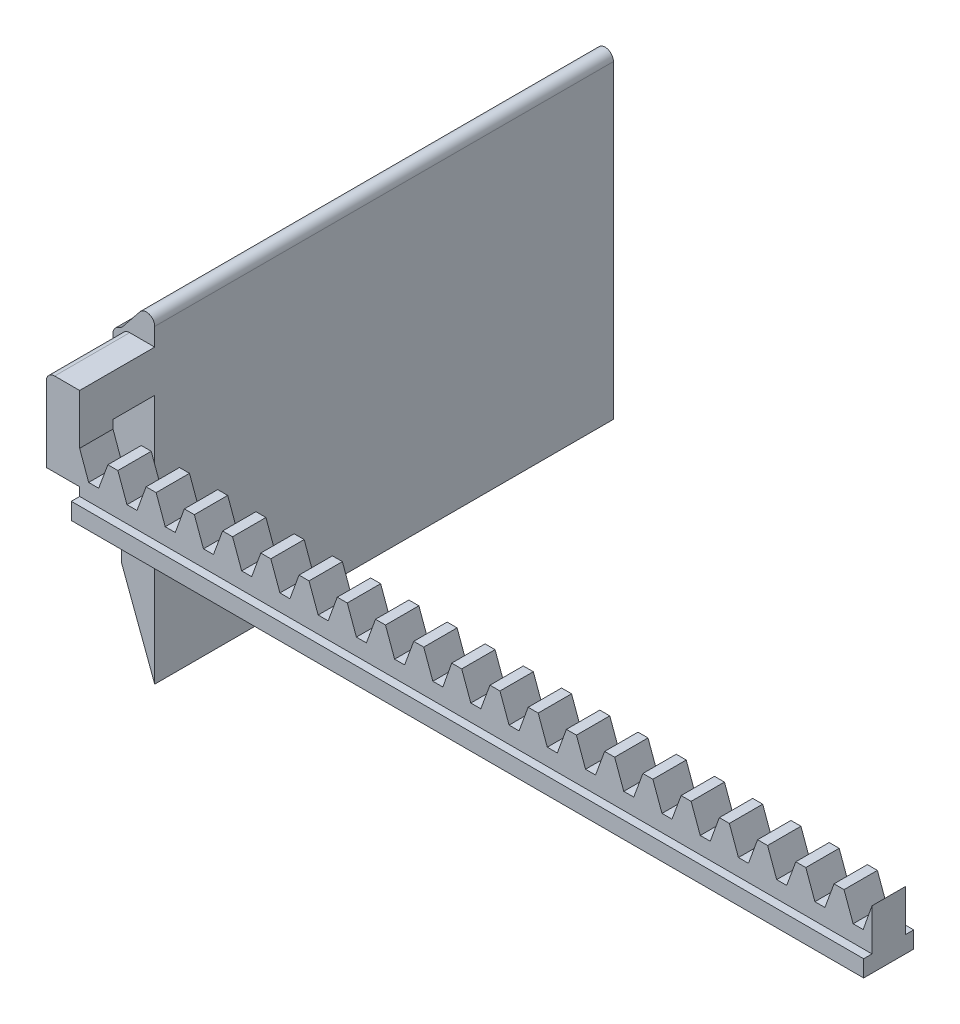
SolidWorks part; units mm, degrees
ref_plane "Plan de face" through (0, 0, 0) normal (0, 0, 1) x (1, 0, 0)
ref_plane "Plan de dessus" through (0, 0, 0) normal (0, 1, 0) x (1, 0, 0)
ref_plane "Plan de droite" through (0, 0, 0) normal (1, 0, 0) x (0, 0, -1)
sketch "Esquisse2" plane through (0, 0, 0) normal (0, 0, 1) x (1, 0, 0)
  line L0 (-0.6, 0) -> (0.6, 0)
  line L1 (-0.6, 0) -> (-1.6919, 3)
  line L2 (0.6, 0) -> (1.6919, 3)
  line L3 (0, 0) -> (0, 2.5065) construction
  line L4 (1.6919, 3) -> (2.8919, 3)
  line L5 (-1.6919, 3) -> (-2.8919, 3)
  line L6 (-47.5, -4) -> (47.5, -4)
  line L7 (3.9838, 0) -> (2.8919, 3)
  line L8 (3.9838, 0) -> (5.1838, 0)
  line L9 (5.1838, 0) -> (6.2757, 3)
  line L10 (8.5676, 0) -> (7.4757, 3)
  line L11 (8.5676, 0) -> (9.7676, 0)
  line L12 (9.7676, 0) -> (10.8596, 3)
  line L13 (13.1515, 0) -> (12.0596, 3)
  line L14 (13.1515, 0) -> (14.3515, 0)
  line L15 (14.3515, 0) -> (15.4434, 3)
  line L16 (17.7353, 0) -> (16.6434, 3)
  line L17 (17.7353, 0) -> (18.9353, 0)
  line L18 (18.9353, 0) -> (20.0272, 3)
  line L19 (22.3191, 0) -> (21.2272, 3)
  line L20 (22.3191, 0) -> (23.5191, 0)
  line L21 (23.5191, 0) -> (24.611, 3)
  line L22 (26.9029, 0) -> (25.811, 3)
  line L23 (26.9029, 0) -> (28.1029, 0)
  line L24 (28.1029, 0) -> (29.1948, 3)
  line L25 (31.4867, 0) -> (30.3948, 3)
  line L26 (31.4867, 0) -> (32.6867, 0)
  line L27 (32.6867, 0) -> (33.7787, 3)
  line L28 (36.0706, 0) -> (34.9787, 3)
  line L29 (36.0706, 0) -> (37.2706, 0)
  line L30 (37.2706, 0) -> (38.3625, 3)
  line L31 (40.6544, 0) -> (39.5625, 3)
  line L32 (40.6544, 0) -> (41.8544, 0)
  line L33 (41.8544, 0) -> (42.9463, 3)
  line L34 (45.2382, 0) -> (44.1463, 3)
  line L35 (45.2382, 0) -> (46.4382, 0)
  line L36 (46.4382, 0) -> (47.5, 3.0001)
  line L40 (6.2757, 3) -> (7.4757, 3)
  line L41 (10.8596, 3) -> (12.0596, 3)
  line L42 (15.4434, 3) -> (16.6434, 3)
  line L43 (20.0272, 3) -> (21.2272, 3)
  line L44 (24.611, 3) -> (25.811, 3)
  line L45 (29.1948, 3) -> (30.3948, 3)
  line L46 (33.7787, 3) -> (34.9787, 3)
  line L47 (38.3625, 3) -> (39.5625, 3)
  line L48 (42.9463, 3) -> (44.1463, 3)
  line L50 (-5.1537, -0.0146) -> (-6.2456, 2.9854)
  line L51 (-3.9537, -0.0146) -> (-2.8919, 3)
  line L52 (-5.1537, -0.0146) -> (-3.9537, -0.0146)
  line L53 (-9.7375, -0.0146) -> (-10.8295, 2.9854)
  line L54 (-8.5375, -0.0146) -> (-7.4456, 2.9854)
  line L55 (-9.7375, -0.0146) -> (-8.5375, -0.0146)
  line L56 (-14.3214, -0.0146) -> (-15.4133, 2.9854)
  line L57 (-13.1214, -0.0146) -> (-12.0295, 2.9854)
  line L58 (-14.3214, -0.0146) -> (-13.1214, -0.0146)
  line L59 (-18.9052, -0.0146) -> (-19.9971, 2.9854)
  line L60 (-17.7052, -0.0146) -> (-16.6133, 2.9854)
  line L61 (-18.9052, -0.0146) -> (-17.7052, -0.0146)
  line L62 (-23.489, -0.0146) -> (-24.5809, 2.9854)
  line L63 (-22.289, -0.0146) -> (-21.1971, 2.9854)
  line L64 (-23.489, -0.0146) -> (-22.289, -0.0146)
  line L65 (-28.0728, -0.0146) -> (-29.1647, 2.9854)
  line L66 (-26.8728, -0.0146) -> (-25.7809, 2.9854)
  line L67 (-28.0728, -0.0146) -> (-26.8728, -0.0146)
  line L68 (-32.6567, -0.0146) -> (-33.7486, 2.9854)
  line L69 (-31.4567, -0.0146) -> (-30.3647, 2.9854)
  line L70 (-32.6567, -0.0146) -> (-31.4567, -0.0146)
  line L71 (-37.2405, -0.0146) -> (-38.3324, 2.9854)
  line L72 (-36.0405, -0.0146) -> (-34.9486, 2.9854)
  line L73 (-37.2405, -0.0146) -> (-36.0405, -0.0146)
  line L74 (-41.8243, -0.0146) -> (-42.9162, 2.9854)
  line L75 (-40.6243, -0.0146) -> (-39.5324, 2.9854)
  line L76 (-41.8243, -0.0146) -> (-40.6243, -0.0146)
  line L77 (-46.421, -0.0047) -> (-47.5, 3)
  line L78 (-45.221, -0.0098) -> (-44.1162, 2.9854)
  line L79 (-46.421, -0.0047) -> (-45.221, -0.0098)
  line L98 (-6.2456, 2.9854) -> (-7.4456, 2.9854)
  line L99 (-42.9162, 2.9854) -> (-44.1162, 2.9854)
  line L100 (-38.3324, 2.9854) -> (-39.5324, 2.9854)
  line L101 (-33.7486, 2.9854) -> (-34.9486, 2.9854)
  line L102 (-29.1647, 2.9854) -> (-30.3647, 2.9854)
  line L103 (-24.5809, 2.9854) -> (-25.7809, 2.9854)
  line L104 (-19.9971, 2.9854) -> (-21.1971, 2.9854)
  line L105 (-15.4133, 2.9854) -> (-16.6133, 2.9854)
  line L106 (-10.8295, 2.9854) -> (-12.0295, 2.9854)
  line L107 (-47.5, -4) -> (-47.5, 3)
  line L108 (47.5, -4) -> (47.5, 3.0001)
  point P4 (0, 0)
  dimension "D1" = 1.2
  dimension "D2" = 3
  dimension "D3" = 40
  dimension "D4" = 1.2
  dimension "D5" = 95
  dimension "D6" = 4
  dimension "D7" = 7
extrude "Boss.-Extru.2" add sketch "Esquisse2" against normal blind 4
sketch "Esquisse5" plane through (-47.5, 0, 0) normal (-1, 0, 0) x (0, 0, 1)
  line L1 (0, -4) -> (1, -4)
  line L2 (0, -4) -> (0, -2)
  line L3 (0, -2) -> (1, -2)
  line L4 (1, -4) -> (1, -2)
  line L5 (-4, -4) -> (-5, -4)
  line L6 (-4, -4) -> (-4, -2)
  line L7 (-4, -2) -> (-5, -2)
  line L8 (-5, -4) -> (-5, -2)
  dimension "D1" = 1
  dimension "D2" = 2
extrude "Boss.-Extru.3" add sketch "Esquisse5" against normal up to surface (95 mm away) up to face at (47.5, -0.5, -2)
sketch "Esquisse6" plane through (0, 0, -4) normal (0, 0, -1) x (-1, 0, 0)
  line L0 (47.5, 3) -> (47.5, -2) construction
  line L1 (47.5, -0.9934) -> (51.5, -0.9934)
  line L2 (47.5, -0.9934) -> (47.5, 9.0066)
  line L3 (47.5, 9.0066) -> (51.5, 9.0066)
  line L4 (51.5, -0.9934) -> (51.5, 9.0066)
  dimension "D1" = 4
  dimension "D2" = 10
extrude "Boss.-Extru.4" add sketch "Esquisse6" against normal up to surface (4 mm away) up to face at (0.013, 1.4123, 0)
sketch "Esquisse7" plane through (-51.5, 0, 0) normal (-1, 0, 0) x (0, 0, 1)
  line L1 (-4, 9.0066) -> (-14, 9.0066)
  line L2 (-4, 9.0066) -> (-4, 4.0066)
  line L3 (-4, 4.0066) -> (-14, 4.0066)
  line L4 (-14, 9.0066) -> (-14, 4.0066)
  dimension "D1" = 10
  dimension "D2" = 5
extrude "Boss.-Extru.5" add sketch "Esquisse7" against normal up to surface (4 mm away) up to face at (-47.5, 6.0033, -2)
sketch "Esquisse8" plane through (0, 0, -14) normal (0, 0, -1) x (-1, 0, 0)
  line L0 (47.5, 14.0066) -> (47.5, -25.9934)
  line L1 (47.5, -25.9934) -> (51.5, -15.3171)
  line L2 (51.5, -15.3171) -> (51.5, -8.9171)
  line L3 (51.5, -8.9171) -> (52.5, -6.248)
  line L4 (52.5, -6.248) -> (52.5, 8.632)
  line L5 (52.5, 8.632) -> (51.5, 9.0066)
  line L6 (51.5, 9.0066) -> (47.5, 14.0066)
  line L7 (47.5, 9.0066) -> (47.5, 4.0066) construction
  line L8 (47.5, 9.0066) -> (51.5, 9.0066) construction
  dimension "D1" = 40
  dimension "D2" = 5
  dimension "D3" = 5
  dimension "D4" = 14.88
  dimension "D5" = 6.4
  dimension "D6" = 5
  dimension "D7" = 0.3747
  dimension "D8" = 2.6691
extrude "Boss.-Extru.6" add sketch "Esquisse8" along normal blind 50 and the other way blind 5
fillet "Congé1" radius 1 6 edges at (-51.5, -15.3171, -36.5) (-51.5, -8.9171, -36.5) (-52.5, -6.248, -36.5) (-52.5, 8.632, -36.5) (-51.5, 9.0066, -36.5) (-47.5, 14.0066, -36.5)
fillet "Congé2" radius 1 1 edges at (-51.5, 9.0066, -4.5)
sketch "Esquisse9" plane through (0, 0, 0) normal (0, 0, 1) x (1, 0, 0)
  line L0 (-47.5, -25.9934) -> (-47.5, 38.4337)
  line L1 (0.1092, 38.4337) -> (-63.8217, 38.4337) construction
  circle A0 centre (0.1092, 19.2137) radius 19.22
  dimension "D1" = 38.44
sketch "Esquisse11" plane through (47.5, 0, 0) normal (1, 0, 0) x (0, 0, -1)
  line L0 (0, -25.9934) -> (0, 38.4337) construction
  line L1 (4, 3.0001) -> (0, 3.0001)
  line L2 (4, 3.0001) -> (4, -4)
  line L3 (4, -4) -> (0, -4)
  line L4 (0, 3.0001) -> (0, -4)
  line L5 (5, -4) -> (-1, -4) construction
  line L7 (5, -2) -> (-1, -2)
  line L8 (5, -2) -> (5, -4)
  line L9 (5, -4) -> (-1, -4)
  line L10 (-1, -2) -> (-1, -4)
